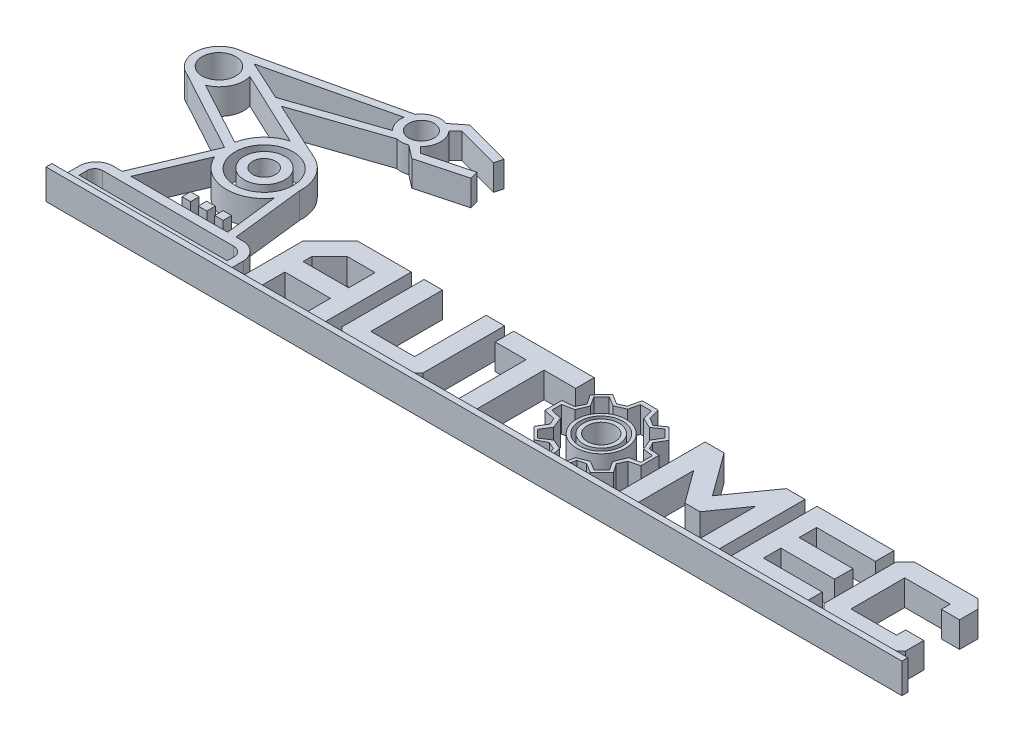
SolidWorks part; units mm, degrees
ref_plane "Front Plane" through (0, 0, 0) normal (0, 0, 1) x (1, 0, 0)
ref_plane "Top Plane" through (0, 0, 0) normal (0, 1, 0) x (1, 0, 0)
ref_plane "Right Plane" through (0, 0, 0) normal (1, 0, 0) x (0, 0, -1)
sketch "Sketch1" plane through (0, 0, 0) normal (0, 1, 0) x (1, 0, 0)
  line L0 (-160.5078, 117.1196) -> (1119.4922, 117.1196) construction
  line L1 (119.1478, 49.1362) -> (109.1101, 49.1362)
  line L2 (138.088, 49.1362) -> (128.2504, 49.1362)
  line L3 (138.088, 49.1362) -> (138.088, 59.0305)
  line L4 (138.088, 59.0305) -> (128.2504, 59.0305)
  line L5 (128.2504, 49.1362) -> (128.2504, 59.0305)
  line L6 (119.1478, 49.1362) -> (119.1478, 59.0305)
  line L7 (119.1478, 59.0305) -> (109.1101, 59.0305)
  line L8 (109.1101, 49.1362) -> (109.1101, 59.0305)
  line L9 (90.1969, 49.1362) -> (100.201, 49.1362)
  line L10 (90.1969, 49.1362) -> (90.1969, 59.0305)
  line L11 (90.1969, 59.0305) -> (100.201, 59.0305)
  line L12 (100.201, 49.1362) -> (100.201, 59.0305)
  line L13 (-20.0667, 231.4486) -> (143.1428, 268.5512)
  line L14 (-1.9691, 225.4726) -> (139.4235, 258.9755)
  line L15 (-1.9691, 225.4726) -> (125.2598, 166.9716)
  line L16 (97.0556, 168.4626) -> (8.3244, 210.1958)
  line L17 (44.4704, 204.1193) -> (146.2196, 238.8776)
  line L18 (56.5759, 198.5531) -> (157.1488, 232.9095)
  line L19 (170.3506, 233.6985) -> (185.6695, 221.8507)
  line L20 (185.6695, 221.8507) -> (240.1758, 236.3182)
  line L21 (240.1758, 236.3182) -> (237.6007, 246.0197)
  line L22 (237.6007, 246.0197) -> (185.6695, 232.2357)
  line L23 (185.6695, 232.2357) -> (178.8357, 239.0896)
  line L24 (170.3506, 277.4089) -> (185.6695, 289.4348)
  line L25 (185.6695, 289.4348) -> (240.1758, 274.7606)
  line L26 (240.1758, 274.7606) -> (237.6007, 265.1957)
  line L27 (237.6007, 265.1957) -> (187.0564, 278.8033)
  line L28 (187.0564, 278.8033) -> (179.3289, 271.5108)
  line L29 (-30.2768, 175.5725) -> (65.1322, 123.7622)
  line L30 (-8.9096, 175.5725) -> (65.9384, 134.9275)
  line L31 (152.7945, 123.7622) -> (162.4199, 39.8389)
  line L33 (145.3839, 101.7) -> (152.7945, 39.8389)
  line L34 (152.7945, 39.8389) -> (39.7561, 39.8389)
  line L35 (39.7561, 39.8389) -> (68.829, 108.4219)
  line L36 (65.1322, 123.7622) -> (29.6656, 39.8389)
  line L37 (29.6656, 39.8389) -> (17.4277, 39.8389)
  line L38 (17.3429, 29.2512) -> (170.3506, 29.2512)
  line L39 (5.5198, 1.6956) -> (187.0564, 1.6956)
  line L40 (8.3244, 20.2328) -> (8.3244, 10.7137)
  line L41 (8.3244, 10.7137) -> (181.3721, 10.7137)
  line L42 (181.3721, 10.7137) -> (181.3721, 20.2328)
  line L43 (190.9922, 20.2328) -> (190.9922, 6.6993)
  line L44 (-0.9281, 6.6993) -> (-0.9281, 20.2328)
  line L45 (162.4199, 39.8389) -> (170.3506, 39.8389)
  line L46 (205.5248, 1.6956) -> (226.324, 1.6956)
  line L47 (226.324, 1.6956) -> (226.324, 32.9725)
  line L48 (226.324, 32.9725) -> (279.552, 32.9725)
  line L49 (279.552, 32.9725) -> (279.552, 1.6956)
  line L50 (279.552, 1.6956) -> (300.1275, 1.6956)
  line L51 (300.1275, 1.6956) -> (300.1275, 106.776)
  line L52 (300.1275, 106.776) -> (237.6007, 106.776)
  line L53 (237.6007, 106.776) -> (205.5248, 74.7001)
  line L54 (205.5248, 74.7001) -> (205.5248, 1.6956)
  line L55 (226.324, 54.2358) -> (279.552, 54.2358)
  line L56 (279.552, 54.2358) -> (279.552, 85.0823)
  line L57 (279.552, 85.0823) -> (246.6759, 85.0823)
  line L58 (246.6759, 85.0823) -> (226.324, 64.7304)
  line L59 (226.324, 64.7304) -> (226.324, 54.2358)
  line L60 (315.1119, 106.776) -> (315.1119, 10.7137)
  line L61 (315.1119, 10.7137) -> (324.1299, 1.6956)
  line L62 (324.1299, 1.6956) -> (398.9795, 1.6956)
  line L63 (398.9795, 1.6956) -> (409.0268, 11.7429)
  line L64 (409.0268, 11.7429) -> (409.0268, 106.776)
  line L65 (409.0268, 106.776) -> (387.5735, 106.776)
  line L66 (387.5735, 106.776) -> (387.5735, 23.1489)
  line L67 (387.5735, 23.1489) -> (336.5651, 23.1489)
  line L68 (336.5651, 23.1489) -> (336.5651, 106.776)
  line L69 (336.5651, 106.776) -> (315.1119, 106.776)
  line L70 (419.7787, 106.776) -> (513.7104, 106.776)
  line L71 (513.7104, 106.776) -> (513.7104, 85.0823)
  line L72 (513.7104, 85.0823) -> (476.8086, 85.0823)
  line L73 (476.8086, 85.0823) -> (476.8086, 1.6956)
  line L74 (476.8086, 1.6956) -> (455.7858, 1.6956)
  line L75 (455.7858, 1.6956) -> (455.7858, 85.0823)
  line L76 (455.7858, 85.0823) -> (419.7787, 85.0823)
  line L77 (419.7787, 85.0823) -> (419.7787, 106.776)
  line L78 (643.4257, 1.6956) -> (665.5667, 1.6956)
  line L79 (665.5667, 1.6956) -> (665.5667, 70.9925)
  line L80 (665.5667, 70.9925) -> (693.2989, 32.9725)
  line L81 (693.2989, 32.9725) -> (710.9671, 32.9725)
  line L82 (710.9671, 32.9725) -> (738.0283, 70.9925)
  line L83 (738.0283, 70.9925) -> (738.0283, 1.6956)
  line L84 (738.0283, 1.6956) -> (759.7221, 1.6956)
  line L85 (759.7221, 1.6956) -> (759.7221, 106.776)
  line L86 (759.7221, 106.776) -> (738.0283, 106.776)
  line L87 (738.0283, 106.776) -> (702.133, 56.3446)
  line L88 (702.133, 56.3446) -> (665.5667, 106.4758)
  line L89 (665.5667, 106.4758) -> (643.4257, 106.4758)
  line L90 (643.4257, 106.4758) -> (643.4257, 1.6956)
  line L91 (773.7558, 106.776) -> (773.7558, 1.6956)
  line L92 (773.7558, 1.6956) -> (863.5251, 1.6956)
  line L93 (863.5251, 1.6956) -> (863.5251, 23.1489)
  line L94 (863.5251, 23.1489) -> (794.9173, 23.1489)
  line L95 (794.9173, 23.1489) -> (794.9173, 43.389)
  line L96 (794.9173, 43.389) -> (857.7335, 43.389)
  line L97 (857.7335, 43.389) -> (857.7335, 64.7304)
  line L98 (857.7335, 64.7304) -> (794.9173, 64.7304)
  line L99 (794.9173, 64.7304) -> (794.9173, 85.0823)
  line L100 (794.9173, 85.0823) -> (863.5251, 85.0823)
  line L101 (863.5251, 85.0823) -> (863.5251, 106.776)
  line L102 (863.5251, 106.776) -> (773.7558, 106.776)
  line L103 (886.7287, 107.2679) -> (876.1896, 96.7288)
  line L104 (876.1896, 96.7288) -> (876.1896, 12.2347)
  line L105 (876.1896, 12.2347) -> (886.7287, 1.6956)
  line L106 (886.7287, 1.6956) -> (961.1619, 1.6956)
  line L107 (961.1619, 1.6956) -> (971.701, 12.2347)
  line L108 (971.701, 12.2347) -> (971.701, 33.4644)
  line L109 (971.701, 33.4644) -> (950.4714, 33.4644)
  line L110 (950.4714, 33.4644) -> (950.4714, 22.8495)
  line L111 (950.4714, 22.8495) -> (897.3435, 22.8495)
  line L112 (897.3435, 22.8495) -> (897.3435, 85.5741)
  line L113 (897.3435, 85.5741) -> (950.4714, 85.5741)
  line L114 (950.4714, 85.5741) -> (950.4714, 75.192)
  line L115 (950.4714, 75.192) -> (971.701, 75.192)
  line L116 (971.701, 75.192) -> (971.701, 96.7288)
  line L117 (971.701, 96.7288) -> (961.0862, 107.3436)
  line L118 (961.0862, 107.3436) -> (886.7287, 107.2679)
  line L119 (532.8884, 87.0482) -> (540.0603, 75.9916)
  line L120 (540.0603, 75.9916) -> (534.8308, 63.2915)
  line L121 (534.8308, 63.2915) -> (521.6824, 60.6021)
  line L122 (521.6824, 60.6021) -> (521.6824, 49.1362)
  line L123 (521.6824, 49.1362) -> (534.8308, 46.109)
  line L124 (534.8308, 46.109) -> (540.0603, 32.9725)
  line L125 (540.0603, 32.9725) -> (532.8884, 21.3063)
  line L126 (532.8884, 21.3063) -> (541.8532, 12.6404)
  line L127 (541.8532, 12.6404) -> (553.1827, 19.9892)
  line L128 (553.1827, 19.9892) -> (565.0655, 15.0962)
  line L129 (565.0655, 15.0962) -> (567.0893, 5.2025)
  line L130 (567.0893, 5.2025) -> (581.4886, 5.2025)
  line L131 (581.4886, 5.2025) -> (583.7645, 15.0877)
  line L132 (583.7645, 15.0877) -> (596.0771, 19.9892)
  line L133 (596.0771, 19.9892) -> (607.081, 13.2245)
  line L134 (607.081, 13.2245) -> (615.9249, 22.3734)
  line L135 (615.9249, 22.3734) -> (609.2638, 32.6426)
  line L136 (609.2638, 32.6426) -> (614.8088, 46.109)
  line L137 (614.8088, 46.109) -> (626.509, 48.5022)
  line L138 (626.509, 48.5022) -> (626.509, 61.9468)
  line L139 (626.509, 61.9468) -> (614.8088, 63.2915)
  line L140 (614.8088, 63.2915) -> (609.2638, 75.9916)
  line L141 (609.2638, 75.9916) -> (615.9249, 87.0482)
  line L142 (615.9249, 87.0482) -> (607.081, 96.2369)
  line L143 (607.081, 96.2369) -> (596.0771, 88.6918)
  line L144 (596.0771, 88.6918) -> (583.786, 94.4645)
  line L145 (583.786, 94.4645) -> (580.7007, 106.4758)
  line L146 (580.7007, 106.4758) -> (567.8066, 106.4758)
  line L147 (567.8066, 106.4758) -> (565.0655, 94.4645)
  line L148 (565.0655, 94.4645) -> (553.1827, 89.2763)
  line L149 (553.1827, 89.2763) -> (541.8532, 96.1018)
  line L150 (541.8532, 96.1018) -> (532.8884, 87.0482)
  line L151 (541.8532, 100.4485) -> (528.563, 87.0266)
  line L152 (528.563, 87.0266) -> (536.1443, 75.97)
  line L153 (536.1443, 75.97) -> (531.4962, 66.0735)
  line L154 (531.4962, 66.0735) -> (517.8813, 64.7088)
  line L155 (517.8813, 64.7088) -> (517.8813, 44.9765)
  line L156 (517.8813, 44.9765) -> (531.4962, 41.8695)
  line L157 (531.4962, 41.8695) -> (534.8308, 34.232)
  line L158 (534.8308, 34.232) -> (527.6258, 22.2726)
  line L159 (527.6258, 22.2726) -> (541.2877, 8.7447)
  line L160 (541.2877, 8.7447) -> (553.1827, 15.0746)
  line L161 (553.1827, 15.0746) -> (561.8112, 11.0221)
  line L162 (561.8112, 11.0221) -> (564.2068, 1.6956)
  line L163 (564.2068, 1.6956) -> (584.5489, 1.6956)
  line L164 (584.5489, 1.6956) -> (587.1397, 13.0484)
  line L165 (587.1397, 13.0484) -> (596.0771, 15.3441)
  line L166 (596.0771, 15.3441) -> (607.081, 8.7147)
  line L167 (607.081, 8.7147) -> (620.5843, 22.3518)
  line L168 (620.5843, 22.3518) -> (613.5429, 32.621)
  line L169 (613.5429, 32.621) -> (617.8866, 41.8695)
  line L170 (617.8866, 41.8695) -> (629.9822, 44.9765)
  line L171 (629.9822, 44.9765) -> (629.9822, 66.0735)
  line L172 (629.9822, 66.0735) -> (617.8866, 66.9675)
  line L173 (617.8866, 66.9675) -> (613.5429, 75.13)
  line L174 (613.5429, 75.13) -> (620.7101, 87.0266)
  line L175 (620.7101, 87.0266) -> (607.081, 100.4485)
  line L176 (607.081, 100.4485) -> (596.0771, 92.9033)
  line L177 (596.0771, 92.9033) -> (587.1397, 98.2878)
  line L178 (587.1397, 98.2878) -> (583.786, 111.3437)
  line L179 (583.786, 111.3437) -> (565.0655, 111.3437)
  line L180 (565.0655, 111.3437) -> (561.8112, 97.0829)
  line L181 (561.8112, 97.0829) -> (553.1827, 93.3156)
  line L182 (553.1827, 93.3156) -> (541.8532, 100.4485)
  line L183 (-160.3737, 54.5426) -> (1119.6263, 54.5426) construction
  line L184 (984.8025, 1.6956) -> (-14.2653, 1.6956)
  line L185 (984.8025, 1.6956) -> (984.8025, -5.2109)
  line L186 (984.8025, -5.2109) -> (-14.2653, -5.2109)
  line L187 (-14.2653, 1.6956) -> (-14.2653, -5.2109)
  circle A0 centre (109.3506, 126.2091) radius 23.7059
  circle A1 centre (109.7378, 125.4347) radius 33.9452
  circle A2 centre (108.9634, 126.2091) radius 43.8994
  circle A3 centre (108.9634, 126.2091) radius 13.4416
  circle A5 centre (163.174, 255.5401) radius 14.8411
  circle A6 centre (-19.5932, 202.4912) radius 28.9613
  circle A7 centre (162.4199, 255.5537) radius 23.2496
  circle A8 centre (-20.0667, 202.4852) radius 19.6385
  arc A9 (-0.9281, 20.2328) -> (17.4277, 39.8389) centre (18.7206, 20.2328) cw
  arc A10 (8.3244, 20.2328) -> (17.3429, 29.2512) centre (17.3429, 20.2328) cw
  arc A11 (5.5198, 1.6956) -> (-0.9281, 6.6993) centre (5.5198, 8.352) cw
  arc A12 (190.9922, 6.6993) -> (187.0564, 1.6956) centre (185.8436, 6.6993) cw
  arc A13 (170.3506, 29.2512) -> (181.3721, 20.2328) centre (170.3506, 18.0073) cw
  arc A14 (170.3506, 39.8389) -> (190.9922, 20.2328) centre (170.3506, 19.1699) cw
  circle A15 centre (574.3212, 54.291) radius 16.2547
  circle A18 centre (574.3212, 54.291) radius 28.9365
  circle A19 centre (574.3212, 54.291) radius 20.8606
  circle A20 centre (574.3212, 54.291) radius 25.1729
  point P59 (0, 0)
  point P224 (0, 0)
  point P235 (146.0821, 101.8989)
  point P236 (145.3839, 101.7)
  point P237 (0, 0)
  point P238 (0, 0)
  point P239 (0, 0)
  point P240 (0, 0)
  dimension "D1" = 19.6487
  dimension "D2" = 9.0185
  dimension "D3" = 6.6563
  dimension "D4" = 5.1486
  dimension "D5" = 11.244
  dimension "D6" = 20.669
  dimension "D7" = 5.5198
  dimension "D8" = 8.3244
  dimension "D9" = 17.4277
  dimension "D10" = 18.7206
  dimension "D11" = 29.6656
  dimension "D12" = 39.7561
  dimension "D13" = 44.4704
  dimension "D14" = 56.5759
  dimension "D15" = 65.1322
  dimension "D16" = 65.9384
  dimension "D17" = 68.829
  dimension "D18" = 97.0556
  dimension "D19" = 125.2598
  dimension "D20" = 145.3839
  dimension "D22" = 146.2196
  dimension "D23" = 178.8357
  dimension "D24" = 185.6695
  dimension "D25" = 237.6007
  dimension "D26" = 179.3289
  dimension "D27" = 240.1758
  dimension "D28" = 6.6993
  dimension "D29" = 19.1699
  dimension "D30" = 265.1957
  dimension "D31" = 10.7137
  dimension "D36" = 117.1196
extrude "Boss-Extrude3" add sketch "Sketch1" along normal blind 30 contours A6 A8 | A6 L16 A2 L15 | A7 L13 A6 L14 | A7 A5 | A7 L28 L27 L26 L25 L24 | A7 L19 L20 L21 L22 L23 | A7 L17 L15 L18 | A6 L29 A2 L30 | A2 A1 | A0 A3 | A14 L45 L31 A2 L33 L34 L35 L36 L37 A9 L44 A11 L39 A12 L43 L38 A13 L42 L41 L40 A10 | L5 L2 L3 L4 | L8 L1 L6 L7 | L9 L12 L11 L10 | L53 L54 L46 L47 L48 L49 L50 L51 L52 L59 L58 L57 L56 L55 | L68 L69 L60 L61 L62 L63 L64 L65 L66 L67 | L77 L76 L75 L74 L73 L72 L71 L70 | L181 L182 L151 L152 L153 L154 L155 L156 L157 L158 L159 L160 L161 L162 L163 L164 L165 L166 L167 L168 L169 L170 L171 L172 L173 L174 L175 L176 L177 L178 L179 L180 L150 L149 L148 L147 L146 L145 L144 L143 L142 L141 L140 L139 L138 L137 L136 L135 L134 L133 | A18 A20 | A19 A15 | L89 L90 L78 L79 L80 L81 L82 L83 L84 L85 L86 L87 L88 | L101 L102 L91 L92 L93 L94 L95 L96 L97 L98 L99 L100 | L117 L118 L103 L104 L105 L106 L107 L108 L109 L110 L111 L112 L113 L114 L115 L116 region at (114.129, 0, -54.0833) region at (133.1692, 0, -54.0833) region at (95.199, 0, -54.0833) region at (63.9522, 0, -245.9386) region at (-10.7691, 0, -229.2141) region at (155.4262, 0, -277.036) region at (57.1544, 0, -193.0736) region at (23.9269, 0, -151.7236) region at (205.95, 0, -277.66) region at (100.7263, 0, -218.4972) region at (96.3539, 0, -35.875) region at (66.4164, 0, -129.2812) region at (206.3681, 0, -233.5548) region at (206.9387, 0, -38.1979) region at (923.9453, 0, -3.1198) region at (320.6174, 0, -7.2012) region at (813.3287, 0, -54.2779) region at (466.5377, 0, -71.6321) region at (748.8752, 0, -3.263) region at (564.5278, 0, -6.749) region at (86.3152, 0, -126.2091) region at (546.2031, 0, -54.291) region at (554.0506, 0, -54.291)
extrude "Boss-Extrude4" add sketch "Sketch1<9>" along normal blind 35 contours L184 L187 L186 L185 L106 L92 L84 L78 L163 L74 L62 L50 L46 L39 region at (485.2686, 0, 1.7576)
sketch "Sketch1<9>" plane through (0, 0, 0) normal (0, 1, 0) x (1, 0, 0) same geometry as "Sketch1"
